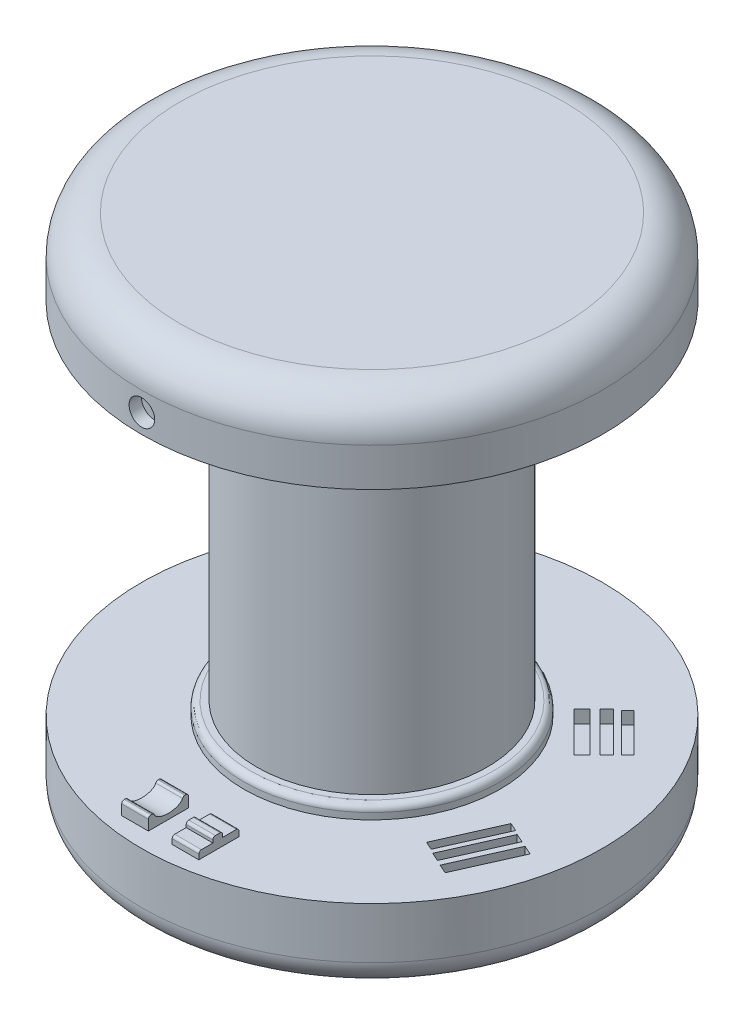
SolidWorks part; units mm, degrees
ref_plane "Front Plane" through (0, 0, 0) normal (0, 0, 1) x (1, 0, 0)
ref_plane "Top Plane" through (0, 0, 0) normal (0, 1, 0) x (1, 0, 0)
ref_plane "Right Plane" through (0, 0, 0) normal (1, 0, 0) x (0, 0, -1)
sketch "Sketch1" plane through (0, 0, 0) normal (0, 1, 0) x (1, 0, 0)
  circle A0 centre (0, 0) radius 180
extrude "Boss-Extrude1" add sketch "Sketch1" along normal blind 60
fillet "Fillet1" radius 20 1 edges at (0, 0, 180)
sketch "Sketch2" plane through (0, 60, 0) normal (0, 1, 0) x (1, 0, 0)
  circle A0 centre (0, 0) radius 100
extrude "Boss-Extrude3" add sketch "Sketch2" along normal blind 10
sketch "Sketch3" plane through (0, 70, 0) normal (0, 1, 0) x (1, 0, 0)
  circle A0 centre (0, 0) radius 90
extrude "Boss-Extrude4" add sketch "Sketch3" along normal blind 270
sketch "Sketch4" plane through (0, 340, 0) normal (0, 1, 0) x (1, 0, 0)
  circle A0 centre (0, 0) radius 180
extrude "Boss-Extrude5" add sketch "Sketch4" along normal blind 60
fillet "Fillet2" radius 30 1 edges at (0, 400, 180)
sketch "Sketch6" plane through (0, 340, 0) normal (0, -1, 0) x (1, 0, 0)
  circle A0 centre (0, 0) radius 100
extrude "Boss-Extrude6" add sketch "Sketch6" along normal blind 10
fillet "Fillet3" radius 5 2 edges at (0, 330, -100) (0, 70, 100)
sketch "Sketch9" plane through (0, 60, 0) normal (0, 1, 0) x (1, 0, 0)
  line L0 (-174.0139, 0) -> (0, 0) construction
  line L1 (0, 172.8944) -> (0, -204.1626) construction
  line L3 (-29.9352, -134.2691) -> (-9.0898, -134.2691)
  line L4 (-29.9352, -134.2691) -> (-29.9352, -165.5372)
  line L5 (-29.9352, -165.5372) -> (-9.0898, -165.5372)
  line L6 (-9.0898, -134.2691) -> (-9.0898, -165.5372)
  line L10 (9.2335, -134.0371) -> (30.0789, -134.0371)
  line L11 (9.2335, -134.0371) -> (9.2335, -165.3052)
  line L12 (9.2335, -165.3052) -> (30.0789, -165.3052)
  line L13 (30.0789, -134.0371) -> (30.0789, -165.3052)
  line L14 (35.0535, 0) -> (198.1383, 0) construction
extrude "Boss-Extrude7" add sketch "Sketch9" along normal blind 10
ref_plane "Plane1" through (0, 0, 180) normal (0, 0, 1) x (1, 0, 0)
sketch "Sketch10" plane through (0, 0, 180) normal (0, 0, 1) x (1, 0, 0)
  line L0 (0, -47.284) -> (0, 416.5608) construction
  line L1 (150, 400) -> (-150, 400) construction
  circle A0 centre (0, 355) radius 10
  dimension "D1" = 45
extrude "Cut-Extrude2" cut sketch "Sketch10" against normal blind 10
ref_plane "Plane2" through (0, 0, -180) normal (0, 0, 1) x (1, 0, 0)
sketch "Sketch12" plane through (0, 0, -180) normal (0, 0, 1) x (1, 0, 0)
  circle A0 centre (0, 355) radius 10
extrude "Cut-Extrude3" cut sketch "Sketch12" along normal blind 10
sketch "Sketch13" plane through (-29.9352, 0, 0) normal (-1, 0, 0) x (0, 0, 1)
  line L1 (134.2691, 70) -> (165.5372, 70) construction
  ellipse E0 centre (149.9031, 70) end of major axis (161.1637, 70) minor radius 5.7775
extrude "Cut-Extrude4" cut sketch "Sketch13" against normal blind 30
sketch "Sketch14" plane through (30.0789, 0, 0) normal (1, 0, 0) x (0, 0, -1)
  line L0 (-165.3052, 65.928) -> (-154.3671, 65.928)
  line L1 (-165.3052, 70) -> (-165.3052, 60) construction
  line L2 (-154.3671, 65.928) -> (-154.3671, 70)
  line L3 (-165.3052, 70) -> (-134.0371, 70) construction
  line L4 (-154.3671, 70) -> (-146.7634, 70)
  line L5 (-146.7634, 70) -> (-146.7634, 65.928)
  line L6 (-146.7634, 65.928) -> (-134.0371, 65.928)
  line L7 (-134.0371, 70) -> (-134.0371, 60) construction
  line L8 (-134.0371, 65.928) -> (-134.0371, 70)
  line L9 (-134.0371, 70) -> (-146.7634, 70)
  line L10 (-165.3052, 70) -> (-165.3052, 65.928)
  line M2 (-134.0371, 60) -> (-134.0371, 70)
  line M3 (-134.0371, 70) -> (-165.3052, 70)
  line M4 (-165.3052, 70) -> (-165.3052, 60)
extrude "Cut-Extrude5" cut sketch "Sketch14" against normal blind 30 contours L0 L2 M3 M4 | L5 L6 M2 M3 region at (30.0789, 67.964, 159.8362) region at (30.0789, 67.964, 140.4002)
fillet "Fillet4" radius 2 8 edges at (-19.5125, 70, 165.5372) (-19.5125, 70, 134.2691) (-19.5125, 70, 138.6426) (-19.5125, 70, 161.1637) (19.6562, 65.928, 134.0371) (19.6562, 65.928, 165.3052) (19.6562, 70, 146.7634) (19.6562, 70, 154.3671)
sketch "Sketch22" plane through (0, 60, 0) normal (0, 1, 0) x (1, 0, 0)
  line L0 (-38.7568, 0) -> (195.2381, 0) construction
  line L1 (127.4238, -18.8725) -> (107.1352, -64.5218)
  line L2 (107.1352, -64.5218) -> (113.6296, -67.4082)
  line L3 (113.6296, -67.4082) -> (133.9182, -21.7589)
  line L4 (133.9182, -21.7589) -> (127.4238, -18.8725)
  line L5 (137.2209, -23.8837) -> (116.9323, -69.533)
  line L6 (116.9323, -69.533) -> (123.6777, -72.531)
  line L7 (123.6777, -72.531) -> (143.9663, -26.8817)
  line L8 (143.9663, -26.8817) -> (137.2209, -23.8837)
  line L9 (148.2654, -28.7768) -> (127.8585, -74.6923)
  line L10 (127.8585, -74.6923) -> (134.9826, -77.8586)
  line L11 (134.9826, -77.8586) -> (155.3895, -31.943)
  line L12 (155.3895, -31.943) -> (148.2654, -28.7768)
  point P16 (154.025, -30.3512)
extrude "Cut-Extrude6" cut sketch "Sketch22" against normal blind 10
sketch "Sketch24" plane through (0, 60, 0) normal (0, 1, 0) x (1, 0, 0)
  line L0 (111.7138, 58.5051) -> (105.5789, 52.3702)
  line L1 (105.5789, 52.3702) -> (74.7294, 83.2198)
  line L2 (74.7294, 83.2198) -> (80.8642, 89.3546)
  line L3 (80.8642, 89.3546) -> (111.7138, 58.5051)
  line L4 (115.57, 62.3613) -> (84.7204, 93.2108)
  line L5 (84.7204, 93.2108) -> (90.1542, 98.6446)
  line L6 (90.1542, 98.6446) -> (121.0037, 67.795)
  line L7 (121.0037, 67.795) -> (115.57, 62.3613)
  line L8 (93.9301, 100.8316) -> (123.9852, 70.7765)
  line L9 (123.9852, 70.7765) -> (128.8735, 75.6649)
  line L10 (128.8735, 75.6649) -> (98.8185, 105.7199)
  line L11 (98.8185, 105.7199) -> (93.9301, 100.8316)
extrude "Cut-Extrude7" cut sketch "Sketch24" against normal blind 10
